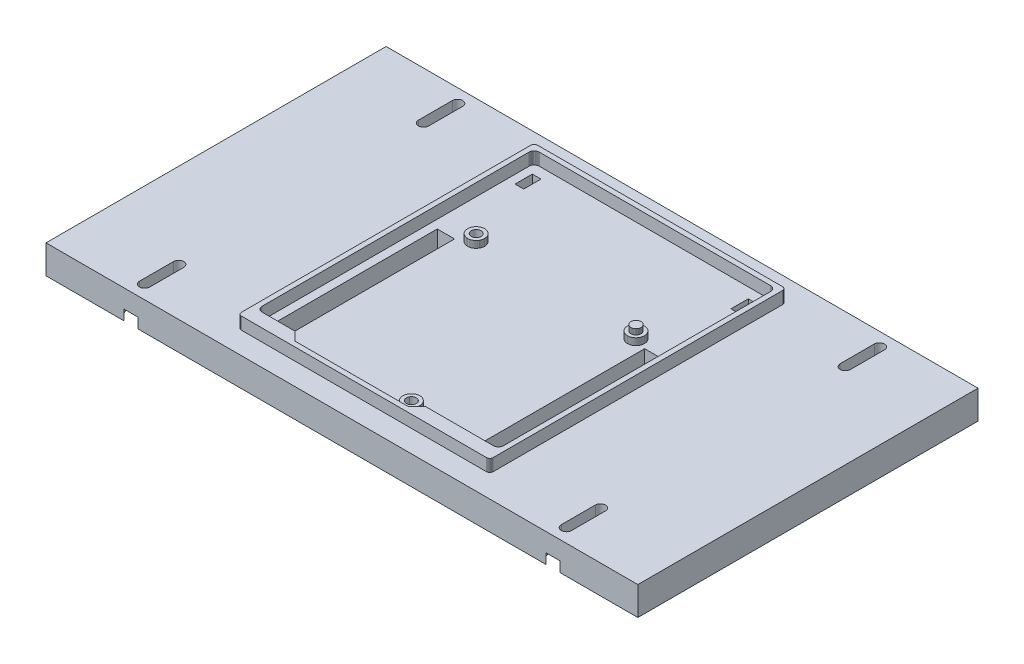
SolidWorks part; units mm, degrees
ref_plane "Front Plane" through (0, 0, 0) normal (0, 0, 1) x (1, 0, 0)
ref_plane "Top Plane" through (0, 0, 0) normal (0, 1, 0) x (1, 0, 0)
ref_plane "Right Plane" through (0, 0, 0) normal (1, 0, 0) x (0, 0, -1)
ref_plane "Plane1" through (0, 0, 0) normal (0, -1, 0) x (1, 0, 0)
sketch "Sketch1" plane through (0, 0, 0) normal (0, -1, 0) x (1, 0, 0)
  line L0 (73, 87.04) -> (1, 87.04)
  line L1 (1, 87.04) -> (0.8264, 87.0248)
  line L2 (0.8264, 87.0248) -> (0.658, 86.9797)
  line L3 (0.658, 86.9797) -> (0.5, 86.906)
  line L4 (0.5, 86.906) -> (0.3572, 86.806)
  line L5 (0.3572, 86.806) -> (0.234, 86.6828)
  line L6 (0.234, 86.6828) -> (0.134, 86.54)
  line L7 (0.134, 86.54) -> (0.0603, 86.382)
  line L8 (0.0603, 86.382) -> (0.0152, 86.2136)
  line L9 (0.0152, 86.2136) -> (0, 86.04)
  line L10 (0, 86.04) -> (0, 1)
  line L11 (0, 1) -> (0.0152, 0.8264)
  line L12 (0.0152, 0.8264) -> (0.0603, 0.658)
  line L13 (0.0603, 0.658) -> (0.134, 0.5)
  line L14 (0.134, 0.5) -> (0.234, 0.3572)
  line L15 (0.234, 0.3572) -> (0.3572, 0.234)
  line L16 (0.3572, 0.234) -> (0.5, 0.134)
  line L17 (0.5, 0.134) -> (0.658, 0.0603)
  line L18 (0.658, 0.0603) -> (0.8264, 0.0152)
  line L19 (0.8264, 0.0152) -> (1, 0)
  line L20 (1, 0) -> (73, 0)
  line L21 (73, 0) -> (73.1736, 0.0152)
  line L22 (73.1736, 0.0152) -> (73.342, 0.0603)
  line L23 (73.342, 0.0603) -> (73.5, 0.134)
  line L24 (73.5, 0.134) -> (73.6428, 0.234)
  line L25 (73.6428, 0.234) -> (73.766, 0.3572)
  line L26 (73.766, 0.3572) -> (73.866, 0.5)
  line L27 (73.866, 0.5) -> (73.9397, 0.658)
  line L28 (73.9397, 0.658) -> (73.9848, 0.8264)
  line L29 (73.9848, 0.8264) -> (74, 1)
  line L30 (74, 1) -> (74, 86.04)
  line L31 (74, 86.04) -> (73.9848, 86.2136)
  line L32 (73.9848, 86.2136) -> (73.9397, 86.382)
  line L33 (73.9397, 86.382) -> (73.866, 86.54)
  line L34 (73.866, 86.54) -> (73.766, 86.6828)
  line L35 (73.766, 86.6828) -> (73.6428, 86.806)
  line L36 (73.6428, 86.806) -> (73.5, 86.906)
  line L37 (73.5, 86.906) -> (73.342, 86.9797)
  line L38 (73.342, 86.9797) -> (73.1736, 87.0248)
  line L39 (73.1736, 87.0248) -> (73, 87.04)
extrude "Boss-Extrude1" add sketch "Sketch1" against normal blind 12
sketch "Sketch2" plane through (0, 12, 0) normal (0, 1, 0) x (-1, 0, 0)
  line L0 (-72.4772, 81.7605) -> (-72.5, 81.5)
  line L1 (-72.5, 81.5) -> (-72.5, 3)
  line L2 (-72.5, 3) -> (-72.4815, 2.7653)
  line L3 (-72.4815, 2.7653) -> (-72.4266, 2.5365)
  line L4 (-72.4266, 2.5365) -> (-72.3365, 2.319)
  line L5 (-72.3365, 2.319) -> (-72.2135, 2.1183)
  line L6 (-72.2135, 2.1183) -> (-72.0607, 1.9393)
  line L7 (-72.0607, 1.9393) -> (-71.8817, 1.7865)
  line L8 (-71.8817, 1.7865) -> (-71.681, 1.6635)
  line L9 (-71.681, 1.6635) -> (-71.4635, 1.5734)
  line L10 (-71.4635, 1.5734) -> (-71.2347, 1.5185)
  line L11 (-71.2347, 1.5185) -> (-71, 1.5)
  line L12 (-71, 1.5) -> (-3, 1.5)
  line L13 (-3, 1.5) -> (-2.7654, 1.5185)
  line L14 (-2.7654, 1.5185) -> (-2.5365, 1.5734)
  line L15 (-2.5365, 1.5734) -> (-2.319, 1.6635)
  line L16 (-2.319, 1.6635) -> (-2.1183, 1.7865)
  line L17 (-2.1183, 1.7865) -> (-1.9393, 1.9393)
  line L18 (-1.9393, 1.9393) -> (-1.7865, 2.1183)
  line L19 (-1.7865, 2.1183) -> (-1.6635, 2.319)
  line L20 (-1.6635, 2.319) -> (-1.5734, 2.5365)
  line L21 (-1.5734, 2.5365) -> (-1.5185, 2.7653)
  line L22 (-1.5185, 2.7653) -> (-1.5, 3)
  line L23 (-1.5, 3) -> (-1.5, 81.5)
  line L24 (-1.5, 81.5) -> (-1.5228, 81.7605)
  line L25 (-1.5228, 81.7605) -> (-1.5905, 82.013)
  line L26 (-1.5905, 82.013) -> (-1.701, 82.25)
  line L27 (-1.701, 82.25) -> (-1.8509, 82.4642)
  line L28 (-1.8509, 82.4642) -> (-2.0358, 82.6491)
  line L29 (-2.0358, 82.6491) -> (-2.25, 82.799)
  line L30 (-2.25, 82.799) -> (-2.487, 82.9095)
  line L31 (-2.487, 82.9095) -> (-2.7395, 82.9772)
  line L32 (-2.7395, 82.9772) -> (-3, 83)
  line L33 (-3, 83) -> (-12.6629, 83)
  line L34 (-12.6629, 83) -> (-15.2029, 85.54)
  line L35 (-15.2029, 85.54) -> (-48.6171, 85.54)
  line L36 (-48.6171, 85.54) -> (-51.1571, 83)
  line L37 (-51.1571, 83) -> (-71, 83)
  line L38 (-71, 83) -> (-71.2605, 82.9772)
  line L39 (-71.2605, 82.9772) -> (-71.513, 82.9095)
  line L40 (-71.513, 82.9095) -> (-71.75, 82.799)
  line L41 (-71.75, 82.799) -> (-71.9642, 82.6491)
  line L42 (-71.9642, 82.6491) -> (-72.1491, 82.4642)
  line L43 (-72.1491, 82.4642) -> (-72.299, 82.25)
  line L44 (-72.299, 82.25) -> (-72.4095, 82.013)
  line L45 (-72.4095, 82.013) -> (-72.4772, 81.7605)
extrude "Cut-Extrude1" cut sketch "Sketch2" against normal blind 3.6
sketch "Sketch3" plane through (0, 8.4, 0) normal (0, 1, 0) x (-1, 0, 0)
  line L0 (-60.6959, 33.662) -> (-60.2749, 33.5492)
  line L1 (-60.2749, 33.5492) -> (-59.88, 33.3651)
  line L2 (-59.88, 33.3651) -> (-59.523, 33.1151)
  line L3 (-59.523, 33.1151) -> (-59.2149, 32.807)
  line L4 (-59.2149, 32.807) -> (-58.9649, 32.45)
  line L5 (-58.9649, 32.45) -> (-58.7808, 32.0551)
  line L6 (-58.7808, 32.0551) -> (-58.668, 31.6341)
  line L7 (-58.668, 31.6341) -> (-58.63, 31.2)
  line L8 (-58.63, 31.2) -> (-58.668, 30.7659)
  line L9 (-58.668, 30.7659) -> (-58.7808, 30.345)
  line L10 (-58.7808, 30.345) -> (-58.9649, 29.95)
  line L11 (-58.9649, 29.95) -> (-59.2149, 29.593)
  line L12 (-59.2149, 29.593) -> (-59.523, 29.2849)
  line L13 (-59.523, 29.2849) -> (-59.88, 29.0349)
  line L14 (-59.88, 29.0349) -> (-60.2749, 28.8508)
  line L15 (-60.2749, 28.8508) -> (-60.6959, 28.738)
  line L16 (-60.6959, 28.738) -> (-61.13, 28.7)
  line L17 (-61.13, 28.7) -> (-61.5641, 28.738)
  line L18 (-61.5641, 28.738) -> (-61.985, 28.8508)
  line L19 (-61.985, 28.8508) -> (-62.38, 29.0349)
  line L20 (-62.38, 29.0349) -> (-62.737, 29.2849)
  line L21 (-62.737, 29.2849) -> (-63.0451, 29.593)
  line L22 (-63.0451, 29.593) -> (-63.2951, 29.95)
  line L23 (-63.2951, 29.95) -> (-63.4792, 30.345)
  line L24 (-63.4792, 30.345) -> (-63.592, 30.7659)
  line L25 (-63.592, 30.7659) -> (-63.63, 31.2)
  line L26 (-63.63, 31.2) -> (-63.592, 31.6341)
  line L27 (-63.592, 31.6341) -> (-63.4792, 32.0551)
  line L28 (-63.4792, 32.0551) -> (-63.2951, 32.45)
  line L29 (-63.2951, 32.45) -> (-63.0451, 32.807)
  line L30 (-63.0451, 32.807) -> (-62.737, 33.1151)
  line L31 (-62.737, 33.1151) -> (-62.38, 33.3651)
  line L32 (-62.38, 33.3651) -> (-61.985, 33.5492)
  line L33 (-61.985, 33.5492) -> (-61.5641, 33.662)
  line L34 (-61.5641, 33.662) -> (-61.13, 33.7)
  line L35 (-61.13, 33.7) -> (-60.6959, 33.662)
extrude "Boss-Extrude2" add sketch "Sketch3" along normal blind 2
sketch "Sketch4" plane through (0, 10.4, 0) normal (0, 1, 0) x (-1, 0, 0)
  line L0 (-61.13, 32.7) -> (-60.8695, 32.6772)
  line L1 (-60.8695, 32.6772) -> (-60.617, 32.6095)
  line L2 (-60.617, 32.6095) -> (-60.38, 32.499)
  line L3 (-60.38, 32.499) -> (-60.1658, 32.3491)
  line L4 (-60.1658, 32.3491) -> (-59.9809, 32.1642)
  line L5 (-59.9809, 32.1642) -> (-59.831, 31.95)
  line L6 (-59.831, 31.95) -> (-59.7205, 31.713)
  line L7 (-59.7205, 31.713) -> (-59.6528, 31.4605)
  line L8 (-59.6528, 31.4605) -> (-59.63, 31.2)
  line L9 (-59.63, 31.2) -> (-59.6528, 30.9395)
  line L10 (-59.6528, 30.9395) -> (-59.7205, 30.687)
  line L11 (-59.7205, 30.687) -> (-59.831, 30.45)
  line L12 (-59.831, 30.45) -> (-59.9809, 30.2358)
  line L13 (-59.9809, 30.2358) -> (-60.1658, 30.0509)
  line L14 (-60.1658, 30.0509) -> (-60.38, 29.901)
  line L15 (-60.38, 29.901) -> (-60.617, 29.7905)
  line L16 (-60.617, 29.7905) -> (-60.8695, 29.7228)
  line L17 (-60.8695, 29.7228) -> (-61.13, 29.7)
  line L18 (-61.13, 29.7) -> (-61.3905, 29.7228)
  line L19 (-61.3905, 29.7228) -> (-61.643, 29.7905)
  line L20 (-61.643, 29.7905) -> (-61.88, 29.901)
  line L21 (-61.88, 29.901) -> (-62.0942, 30.0509)
  line L22 (-62.0942, 30.0509) -> (-62.2791, 30.2358)
  line L23 (-62.2791, 30.2358) -> (-62.429, 30.45)
  line L24 (-62.429, 30.45) -> (-62.5395, 30.687)
  line L25 (-62.5395, 30.687) -> (-62.6072, 30.9395)
  line L26 (-62.6072, 30.9395) -> (-62.63, 31.2)
  line L27 (-62.63, 31.2) -> (-62.6072, 31.4605)
  line L28 (-62.6072, 31.4605) -> (-62.5395, 31.713)
  line L29 (-62.5395, 31.713) -> (-62.429, 31.95)
  line L30 (-62.429, 31.95) -> (-62.2791, 32.1642)
  line L31 (-62.2791, 32.1642) -> (-62.0942, 32.3491)
  line L32 (-62.0942, 32.3491) -> (-61.88, 32.499)
  line L33 (-61.88, 32.499) -> (-61.643, 32.6095)
  line L34 (-61.643, 32.6095) -> (-61.3905, 32.6772)
  line L35 (-61.3905, 32.6772) -> (-61.13, 32.7)
extrude "Boss-Extrude3" add sketch "Sketch4" along normal blind 1.6
sketch "Sketch5" plane through (0, 8.4, 0) normal (0, 1, 0) x (-1, 0, 0)
  line L0 (-14.477, 28.0149) -> (-14.7851, 28.323)
  line L1 (-14.7851, 28.323) -> (-15.0351, 28.68)
  line L2 (-15.0351, 28.68) -> (-15.2192, 29.075)
  line L3 (-15.2192, 29.075) -> (-15.332, 29.4959)
  line L4 (-15.332, 29.4959) -> (-15.37, 29.93)
  line L5 (-15.37, 29.93) -> (-15.332, 30.3641)
  line L6 (-15.332, 30.3641) -> (-15.2192, 30.7851)
  line L7 (-15.2192, 30.7851) -> (-15.0351, 31.18)
  line L8 (-15.0351, 31.18) -> (-14.7851, 31.537)
  line L9 (-14.7851, 31.537) -> (-14.477, 31.8451)
  line L10 (-14.477, 31.8451) -> (-14.12, 32.0951)
  line L11 (-14.12, 32.0951) -> (-13.7251, 32.2792)
  line L12 (-13.7251, 32.2792) -> (-13.3041, 32.392)
  line L13 (-13.3041, 32.392) -> (-12.87, 32.43)
  line L14 (-12.87, 32.43) -> (-12.4359, 32.392)
  line L15 (-12.4359, 32.392) -> (-12.0149, 32.2792)
  line L16 (-12.0149, 32.2792) -> (-11.62, 32.0951)
  line L17 (-11.62, 32.0951) -> (-11.263, 31.8451)
  line L18 (-11.263, 31.8451) -> (-10.9549, 31.537)
  line L19 (-10.9549, 31.537) -> (-10.7049, 31.18)
  line L20 (-10.7049, 31.18) -> (-10.5208, 30.7851)
  line L21 (-10.5208, 30.7851) -> (-10.408, 30.3641)
  line L22 (-10.408, 30.3641) -> (-10.37, 29.93)
  line L23 (-10.37, 29.93) -> (-10.408, 29.4959)
  line L24 (-10.408, 29.4959) -> (-10.5208, 29.075)
  line L25 (-10.5208, 29.075) -> (-10.7049, 28.68)
  line L26 (-10.7049, 28.68) -> (-10.9549, 28.323)
  line L27 (-10.9549, 28.323) -> (-11.263, 28.0149)
  line L28 (-11.263, 28.0149) -> (-11.62, 27.7649)
  line L29 (-11.62, 27.7649) -> (-12.0149, 27.5808)
  line L30 (-12.0149, 27.5808) -> (-12.4359, 27.468)
  line L31 (-12.4359, 27.468) -> (-12.87, 27.43)
  line L32 (-12.87, 27.43) -> (-13.3041, 27.468)
  line L33 (-13.3041, 27.468) -> (-13.7251, 27.5808)
  line L34 (-13.7251, 27.5808) -> (-14.12, 27.7649)
  line L35 (-14.12, 27.7649) -> (-14.477, 28.0149)
extrude "Boss-Extrude4" add sketch "Sketch5" along normal blind 2
sketch "Sketch6" plane through (0, 10.4, 0) normal (0, 1, 0) x (-1, 0, 0)
  line L0 (-12.87, 28.48) -> (-12.6182, 28.502)
  line L1 (-12.6182, 28.502) -> (-12.3741, 28.5674)
  line L2 (-12.3741, 28.5674) -> (-12.145, 28.6743)
  line L3 (-12.145, 28.6743) -> (-11.938, 28.8192)
  line L4 (-11.938, 28.8192) -> (-11.7592, 28.998)
  line L5 (-11.7592, 28.998) -> (-11.6143, 29.205)
  line L6 (-11.6143, 29.205) -> (-11.5074, 29.4341)
  line L7 (-11.5074, 29.4341) -> (-11.442, 29.6782)
  line L8 (-11.442, 29.6782) -> (-11.42, 29.93)
  line L9 (-11.42, 29.93) -> (-11.442, 30.1818)
  line L10 (-11.442, 30.1818) -> (-11.5074, 30.4259)
  line L11 (-11.5074, 30.4259) -> (-11.6143, 30.655)
  line L12 (-11.6143, 30.655) -> (-11.7592, 30.862)
  line L13 (-11.7592, 30.862) -> (-11.938, 31.0408)
  line L14 (-11.938, 31.0408) -> (-12.145, 31.1857)
  line L15 (-12.145, 31.1857) -> (-12.3741, 31.2926)
  line L16 (-12.3741, 31.2926) -> (-12.6182, 31.358)
  line L17 (-12.6182, 31.358) -> (-12.87, 31.38)
  line L18 (-12.87, 31.38) -> (-13.1218, 31.358)
  line L19 (-13.1218, 31.358) -> (-13.3659, 31.2926)
  line L20 (-13.3659, 31.2926) -> (-13.595, 31.1857)
  line L21 (-13.595, 31.1857) -> (-13.802, 31.0408)
  line L22 (-13.802, 31.0408) -> (-13.9808, 30.862)
  line L23 (-13.9808, 30.862) -> (-14.1257, 30.655)
  line L24 (-14.1257, 30.655) -> (-14.2326, 30.4259)
  line L25 (-14.2326, 30.4259) -> (-14.298, 30.1818)
  line L26 (-14.298, 30.1818) -> (-14.32, 29.93)
  line L27 (-14.32, 29.93) -> (-14.298, 29.6782)
  line L28 (-14.298, 29.6782) -> (-14.2326, 29.4341)
  line L29 (-14.2326, 29.4341) -> (-14.1257, 29.205)
  line L30 (-14.1257, 29.205) -> (-13.9808, 28.998)
  line L31 (-13.9808, 28.998) -> (-13.802, 28.8192)
  line L32 (-13.802, 28.8192) -> (-13.595, 28.6743)
  line L33 (-13.595, 28.6743) -> (-13.3659, 28.5674)
  line L34 (-13.3659, 28.5674) -> (-13.1218, 28.502)
  line L35 (-13.1218, 28.502) -> (-12.87, 28.48)
extrude "Cut-Extrude2" cut sketch "Sketch6" against normal blind 8.4
sketch "Sketch7" plane through (0, 8.4, 0) normal (0, 1, 0) x (-1, 0, 0)
  line L0 (-46.3241, 79.538) -> (-46.7451, 79.6508)
  line L1 (-46.7451, 79.6508) -> (-47.14, 79.8349)
  line L2 (-47.14, 79.8349) -> (-47.497, 80.0849)
  line L3 (-47.497, 80.0849) -> (-47.8051, 80.393)
  line L4 (-47.8051, 80.393) -> (-48.0551, 80.75)
  line L5 (-48.0551, 80.75) -> (-48.2392, 81.145)
  line L6 (-48.2392, 81.145) -> (-48.352, 81.5659)
  line L7 (-48.352, 81.5659) -> (-48.39, 82)
  line L8 (-48.39, 82) -> (-48.352, 82.4341)
  line L9 (-48.352, 82.4341) -> (-48.2392, 82.855)
  line L10 (-48.2392, 82.855) -> (-48.0551, 83.25)
  line L11 (-48.0551, 83.25) -> (-47.8051, 83.607)
  line L12 (-47.8051, 83.607) -> (-47.497, 83.9151)
  line L13 (-47.497, 83.9151) -> (-47.14, 84.1651)
  line L14 (-47.14, 84.1651) -> (-46.7451, 84.3492)
  line L15 (-46.7451, 84.3492) -> (-46.3241, 84.462)
  line L16 (-46.3241, 84.462) -> (-45.89, 84.5)
  line L17 (-45.89, 84.5) -> (-45.4559, 84.462)
  line L18 (-45.4559, 84.462) -> (-45.0349, 84.3492)
  line L19 (-45.0349, 84.3492) -> (-44.64, 84.1651)
  line L20 (-44.64, 84.1651) -> (-44.283, 83.9151)
  line L21 (-44.283, 83.9151) -> (-43.9749, 83.607)
  line L22 (-43.9749, 83.607) -> (-43.7249, 83.25)
  line L23 (-43.7249, 83.25) -> (-43.5408, 82.855)
  line L24 (-43.5408, 82.855) -> (-43.428, 82.4341)
  line L25 (-43.428, 82.4341) -> (-43.39, 82)
  line L26 (-43.39, 82) -> (-43.428, 81.5659)
  line L27 (-43.428, 81.5659) -> (-43.5408, 81.145)
  line L28 (-43.5408, 81.145) -> (-43.7249, 80.75)
  line L29 (-43.7249, 80.75) -> (-43.9749, 80.393)
  line L30 (-43.9749, 80.393) -> (-44.283, 80.0849)
  line L31 (-44.283, 80.0849) -> (-44.64, 79.8349)
  line L32 (-44.64, 79.8349) -> (-45.0349, 79.6508)
  line L33 (-45.0349, 79.6508) -> (-45.4559, 79.538)
  line L34 (-45.4559, 79.538) -> (-45.89, 79.5)
  line L35 (-45.89, 79.5) -> (-46.3241, 79.538)
extrude "Boss-Extrude5" add sketch "Sketch7" along normal blind 2
sketch "Sketch8" plane through (0, 10.4, 0) normal (0, 1, 0) x (-1, 0, 0)
  line L0 (-44.462, 82.2518) -> (-44.5274, 82.4959)
  line L1 (-44.5274, 82.4959) -> (-44.6343, 82.725)
  line L2 (-44.6343, 82.725) -> (-44.7792, 82.932)
  line L3 (-44.7792, 82.932) -> (-44.958, 83.1108)
  line L4 (-44.958, 83.1108) -> (-45.165, 83.2557)
  line L5 (-45.165, 83.2557) -> (-45.3941, 83.3626)
  line L6 (-45.3941, 83.3626) -> (-45.6382, 83.428)
  line L7 (-45.6382, 83.428) -> (-45.89, 83.45)
  line L8 (-45.89, 83.45) -> (-46.1418, 83.428)
  line L9 (-46.1418, 83.428) -> (-46.3859, 83.3626)
  line L10 (-46.3859, 83.3626) -> (-46.615, 83.2557)
  line L11 (-46.615, 83.2557) -> (-46.822, 83.1108)
  line L12 (-46.822, 83.1108) -> (-47.0008, 82.932)
  line L13 (-47.0008, 82.932) -> (-47.1457, 82.725)
  line L14 (-47.1457, 82.725) -> (-47.2526, 82.4959)
  line L15 (-47.2526, 82.4959) -> (-47.318, 82.2518)
  line L16 (-47.318, 82.2518) -> (-47.34, 82)
  line L17 (-47.34, 82) -> (-47.318, 81.7482)
  line L18 (-47.318, 81.7482) -> (-47.2526, 81.5041)
  line L19 (-47.2526, 81.5041) -> (-47.1457, 81.275)
  line L20 (-47.1457, 81.275) -> (-47.0008, 81.068)
  line L21 (-47.0008, 81.068) -> (-46.822, 80.8892)
  line L22 (-46.822, 80.8892) -> (-46.615, 80.7443)
  line L23 (-46.615, 80.7443) -> (-46.3859, 80.6374)
  line L24 (-46.3859, 80.6374) -> (-46.1418, 80.572)
  line L25 (-46.1418, 80.572) -> (-45.89, 80.55)
  line L26 (-45.89, 80.55) -> (-45.6382, 80.572)
  line L27 (-45.6382, 80.572) -> (-45.3941, 80.6374)
  line L28 (-45.3941, 80.6374) -> (-45.165, 80.7443)
  line L29 (-45.165, 80.7443) -> (-44.958, 80.8892)
  line L30 (-44.958, 80.8892) -> (-44.7792, 81.068)
  line L31 (-44.7792, 81.068) -> (-44.6343, 81.275)
  line L32 (-44.6343, 81.275) -> (-44.5274, 81.5041)
  line L33 (-44.5274, 81.5041) -> (-44.462, 81.7482)
  line L34 (-44.462, 81.7482) -> (-44.44, 82)
  line L35 (-44.44, 82) -> (-44.462, 82.2518)
extrude "Cut-Extrude3" cut sketch "Sketch8" against normal blind 8.4
sketch "Sketch9" plane through (0, 8.4, 0) normal (0, 1, 0) x (-1, 0, 0)
  line L0 (-67.48, 9.61) -> (-70.02, 9.61)
  line L1 (-70.02, 9.61) -> (-70.02, 4.53)
  line L2 (-70.02, 4.53) -> (-67.48, 4.53)
  line L3 (-67.48, 4.53) -> (-67.48, 9.61)
extrude "Cut-Extrude4" cut sketch "Sketch9" against normal blind 6.4
sketch "Sketch10" plane through (0, 8.4, 0) normal (0, 1, 0) x (-1, 0, 0)
  line L0 (-64.94, 32.47) -> (-64.94, 80.73)
  line L1 (-64.94, 80.73) -> (-70.02, 80.73)
  line L2 (-70.02, 80.73) -> (-70.02, 32.47)
  line L3 (-70.02, 32.47) -> (-64.94, 32.47)
extrude "Cut-Extrude5" cut sketch "Sketch10" against normal blind 6.4
sketch "Sketch11" plane through (0, 8.4, 0) normal (0, 1, 0) x (-1, 0, 0)
  line L0 (-6.52, 4.53) -> (-3.98, 4.53)
  line L1 (-3.98, 4.53) -> (-3.98, 9.61)
  line L2 (-3.98, 9.61) -> (-6.52, 9.61)
  line L3 (-6.52, 9.61) -> (-6.52, 4.53)
extrude "Cut-Extrude6" cut sketch "Sketch11" against normal blind 6.4
sketch "Sketch12" plane through (0, 8.4, 0) normal (0, 1, 0) x (-1, 0, 0)
  line L0 (-3.98, 32.47) -> (-3.98, 80.73)
  line L1 (-3.98, 80.73) -> (-9.06, 80.73)
  line L2 (-9.06, 80.73) -> (-9.06, 32.47)
  line L3 (-9.06, 32.47) -> (-3.98, 32.47)
extrude "Cut-Extrude7" cut sketch "Sketch12" against normal blind 6.4
sketch "Sketch13" plane through (0, 8.4, 0) normal (0, 1, 0) x (1, 0, 0)
  line L0 (73.9848, -0.8264) -> (74, -1) construction
  line L1 (74, -1) -> (74, -86.04) construction
  line L2 (74, -86.04) -> (73.9848, -86.2136) construction
  line L3 (73.9848, -86.2136) -> (73.9397, -86.382) construction
  line L4 (73.9397, -86.382) -> (73.866, -86.54) construction
  line L5 (73.866, -86.54) -> (73.766, -86.6828) construction
  line L6 (73.766, -86.6828) -> (73.6428, -86.806) construction
  line L7 (73.6428, -86.806) -> (73.5, -86.906) construction
  line L8 (73.5, -86.906) -> (73.342, -86.9797) construction
  line L9 (73.342, -86.9797) -> (73.1736, -87.0248) construction
  line L10 (73.1736, -87.0248) -> (73, -87.04) construction
  line L11 (73, -87.04) -> (1, -87.04) construction
  line L12 (73, 0) -> (73.1736, -0.0152) construction
  line L13 (0.8264, -0.0152) -> (1, 0) construction
  line L14 (1, 0) -> (73, 0) construction
  line L15 (73.9848, -0.8264) -> (74, -1)
  line L16 (74, -1) -> (74, -86.04)
  line L17 (74, -86.04) -> (73.9848, -86.2136)
  line L18 (73.9848, -86.2136) -> (73.9397, -86.382)
  line L19 (73.9397, -86.382) -> (73.866, -86.54)
  line L20 (73.866, -86.54) -> (73.766, -86.6828)
  line L21 (73.766, -86.6828) -> (73.6428, -86.806)
  line L22 (73.6428, -86.806) -> (73.5, -86.906)
  line L23 (73.5, -86.906) -> (73.342, -86.9797)
  line L24 (73.342, -86.9797) -> (73.1736, -87.0248)
  line L25 (73.1736, -87.0248) -> (73, -87.04)
  line L26 (73, -87.04) -> (1, -87.04)
  line L27 (73, 0) -> (73.1736, -0.0152)
  line L28 (0.8264, -0.0152) -> (1, 0)
  line L29 (1, 0) -> (73, 0)
  line L30 (73.342, -0.0603) -> (73.5, -0.134) construction
  line L31 (73.5, -0.134) -> (73.6428, -0.234) construction
  line L32 (73.6428, -0.234) -> (73.766, -0.3572) construction
  line L33 (73.766, -0.3572) -> (73.866, -0.5) construction
  line L34 (73.866, -0.5) -> (73.9397, -0.658) construction
  line L35 (73.9397, -0.658) -> (73.9848, -0.8264) construction
  line L36 (73.1736, -0.0152) -> (73.342, -0.0603) construction
  line L37 (73.342, -0.0603) -> (73.5, -0.134)
  line L38 (73.5, -0.134) -> (73.6428, -0.234)
  line L39 (73.6428, -0.234) -> (73.766, -0.3572)
  line L40 (73.766, -0.3572) -> (73.866, -0.5)
  line L41 (73.866, -0.5) -> (73.9397, -0.658)
  line L42 (73.9397, -0.658) -> (73.9848, -0.8264)
  line L43 (73.1736, -0.0152) -> (73.342, -0.0603)
  line L44 (0, -86.04) -> (0, -1) construction
  line L45 (0, -1) -> (0.0152, -0.8264) construction
  line L46 (0.0152, -0.8264) -> (0.0603, -0.658) construction
  line L47 (0.0603, -0.658) -> (0.134, -0.5) construction
  line L48 (0.134, -0.5) -> (0.234, -0.3572) construction
  line L49 (0.234, -0.3572) -> (0.3572, -0.234) construction
  line L50 (0.3572, -0.234) -> (0.5, -0.134) construction
  line L51 (0.5, -0.134) -> (0.658, -0.0603) construction
  line L52 (0.658, -0.0603) -> (0.8264, -0.0152) construction
  line L53 (0, -86.04) -> (0, -1)
  line L54 (0, -1) -> (0.0152, -0.8264)
  line L55 (0.0152, -0.8264) -> (0.0603, -0.658)
  line L56 (0.0603, -0.658) -> (0.134, -0.5)
  line L57 (0.134, -0.5) -> (0.234, -0.3572)
  line L58 (0.234, -0.3572) -> (0.3572, -0.234)
  line L59 (0.3572, -0.234) -> (0.5, -0.134)
  line L60 (0.5, -0.134) -> (0.658, -0.0603)
  line L61 (0.658, -0.0603) -> (0.8264, -0.0152)
  line L62 (1, -87.04) -> (0.8264, -87.0248) construction
  line L63 (0.8264, -87.0248) -> (0.658, -86.9797) construction
  line L64 (0.658, -86.9797) -> (0.5, -86.906) construction
  line L65 (0.5, -86.906) -> (0.3572, -86.806) construction
  line L66 (0.3572, -86.806) -> (0.234, -86.6828) construction
  line L67 (0.234, -86.6828) -> (0.134, -86.54) construction
  line L68 (0.134, -86.54) -> (0.0603, -86.382) construction
  line L69 (0.0603, -86.382) -> (0.0152, -86.2136) construction
  line L70 (0.0152, -86.2136) -> (0, -86.04) construction
  line L71 (1, -87.04) -> (0.8264, -87.0248)
  line L72 (0.8264, -87.0248) -> (0.658, -86.9797)
  line L73 (0.658, -86.9797) -> (0.5, -86.906)
  line L74 (0.5, -86.906) -> (0.3572, -86.806)
  line L75 (0.3572, -86.806) -> (0.234, -86.6828)
  line L76 (0.234, -86.6828) -> (0.134, -86.54)
  line L77 (0.134, -86.54) -> (0.0603, -86.382)
  line L78 (0.0603, -86.382) -> (0.0152, -86.2136)
  line L79 (0.0152, -86.2136) -> (0, -86.04)
  line L80 (37, -87.04) -> (37, -93.52) construction
  line L81 (-50, 6.48) -> (124, 6.48)
  line L82 (-50, 6.48) -> (-50, -93.52)
  line L83 (-50, -93.52) -> (124, -93.52)
  line L84 (124, 6.48) -> (124, -93.52)
  line L85 (37, 0) -> (37, 6.48) construction
  dimension "D1" = 100
  dimension "D2" = 50
extrude "Boss-Extrude6" add sketch "Sketch13" against normal up to surface (8.4 mm away) up to face at (37, 0, 43.52)
sketch "Sketch14" plane through (0, 2, 0) normal (0, 1, 0) x (1, 0, 0)
  line L0 (12.87, -32.43) -> (12.87, -27.43) construction
  line L1 (46.822, -80.8892) -> (46.615, -80.7443) construction
  line L2 (46.615, -80.7443) -> (46.3859, -80.6374) construction
  line L3 (46.3859, -80.6374) -> (46.1418, -80.572) construction
  line L4 (46.1418, -80.572) -> (45.89, -80.55) construction
  line L5 (45.89, -80.55) -> (45.6382, -80.572) construction
  line L6 (45.6382, -80.572) -> (45.3941, -80.6374) construction
  line L7 (45.3941, -80.6374) -> (45.165, -80.7443) construction
  line L8 (45.165, -80.7443) -> (44.958, -80.8892) construction
  line L9 (44.958, -80.8892) -> (44.7792, -81.068) construction
  line L10 (44.7792, -81.068) -> (44.6343, -81.275) construction
  line L11 (44.6343, -81.275) -> (44.5274, -81.5041) construction
  line L12 (44.5274, -81.5041) -> (44.462, -81.7482) construction
  line L13 (44.462, -81.7482) -> (44.44, -82) construction
  line L14 (46.822, -80.8892) -> (46.615, -80.7443) construction
  line L15 (46.615, -80.7443) -> (46.3859, -80.6374) construction
  line L16 (46.3859, -80.6374) -> (46.1418, -80.572) construction
  line L17 (46.1418, -80.572) -> (45.89, -80.55) construction
  line L18 (45.89, -80.55) -> (45.6382, -80.572) construction
  line L19 (45.6382, -80.572) -> (45.3941, -80.6374) construction
  line L20 (45.3941, -80.6374) -> (45.165, -80.7443) construction
  line L21 (45.165, -80.7443) -> (44.958, -80.8892) construction
  line L22 (44.958, -80.8892) -> (44.7792, -81.068) construction
  line L23 (44.7792, -81.068) -> (44.6343, -81.275) construction
  line L24 (44.6343, -81.275) -> (44.5274, -81.5041) construction
  line L25 (44.5274, -81.5041) -> (44.462, -81.7482) construction
  line L26 (44.462, -81.7482) -> (44.44, -82) construction
  line L27 (45.165, -83.2557) -> (45.3941, -83.3626) construction
  line L28 (44.958, -83.1108) -> (45.165, -83.2557) construction
  line L29 (47.0008, -81.068) -> (46.822, -80.8892) construction
  line L30 (44.7792, -82.932) -> (44.958, -83.1108) construction
  line L31 (44.6343, -82.725) -> (44.7792, -82.932) construction
  line L32 (44.6343, -82.725) -> (44.7792, -82.932) construction
  line L33 (44.5274, -82.4959) -> (44.6343, -82.725) construction
  line L34 (44.462, -82.2518) -> (44.5274, -82.4959) construction
  line L35 (44.44, -82) -> (44.462, -82.2518) construction
  line L36 (45.165, -83.2557) -> (45.3941, -83.3626) construction
  line L37 (46.3241, -79.538) -> (45.89, -79.5)
  line L38 (45.89, -79.5) -> (45.4559, -79.538)
  line L39 (45.4559, -79.538) -> (45.0349, -79.6508)
  line L40 (45.0349, -79.6508) -> (44.64, -79.8349)
  line L41 (44.64, -79.8349) -> (44.283, -80.0849)
  line L42 (44.283, -80.0849) -> (43.9749, -80.393)
  line L43 (43.9749, -80.393) -> (43.7249, -80.75)
  line L44 (43.7249, -80.75) -> (43.5408, -81.145)
  line L45 (43.5408, -81.145) -> (43.428, -81.5659)
  line L46 (43.428, -81.5659) -> (43.39, -82)
  line L47 (43.39, -82) -> (43.428, -82.4341)
  line L48 (43.428, -82.4341) -> (43.5408, -82.855)
  line L49 (43.5408, -82.855) -> (43.7249, -83.25)
  line L50 (43.7249, -83.25) -> (43.9749, -83.607)
  line L51 (43.9749, -83.607) -> (44.283, -83.9151)
  line L52 (44.283, -83.9151) -> (44.64, -84.1651)
  line L53 (44.64, -84.1651) -> (45.0349, -84.3492)
  line L54 (45.0349, -84.3492) -> (45.4559, -84.462)
  line L55 (45.4559, -84.462) -> (45.89, -84.5)
  line L56 (45.89, -84.5) -> (46.3241, -84.462)
  line L57 (46.3241, -84.462) -> (46.7451, -84.3492)
  line L58 (46.7451, -84.3492) -> (47.14, -84.1651)
  line L59 (47.14, -84.1651) -> (47.497, -83.9151)
  line L60 (47.497, -83.9151) -> (47.8051, -83.607)
  line L61 (47.8051, -83.607) -> (48.0551, -83.25)
  line L62 (48.0551, -83.25) -> (48.2392, -82.855)
  line L63 (48.2392, -82.855) -> (48.352, -82.4341)
  line L64 (48.352, -82.4341) -> (48.39, -82)
  line L65 (48.39, -82) -> (48.352, -81.5659)
  line L66 (48.352, -81.5659) -> (48.2392, -81.145)
  line L67 (48.2392, -81.145) -> (48.0551, -80.75)
  line L68 (48.0551, -80.75) -> (47.8051, -80.393)
  line L69 (47.8051, -80.393) -> (47.497, -80.0849)
  line L70 (47.497, -80.0849) -> (47.14, -79.8349)
  line L71 (47.14, -79.8349) -> (46.7451, -79.6508)
  line L72 (46.7451, -79.6508) -> (46.3241, -79.538)
  line L73 (46.3241, -79.538) -> (45.89, -79.5) construction
  line L74 (45.89, -79.5) -> (45.4559, -79.538) construction
  line L75 (45.4559, -79.538) -> (45.0349, -79.6508) construction
  line L76 (45.0349, -79.6508) -> (44.64, -79.8349) construction
  line L77 (44.64, -79.8349) -> (44.283, -80.0849) construction
  line L78 (44.283, -80.0849) -> (43.9749, -80.393) construction
  line L79 (43.9749, -80.393) -> (43.7249, -80.75) construction
  line L80 (43.7249, -80.75) -> (43.5408, -81.145) construction
  line L81 (43.5408, -81.145) -> (43.428, -81.5659) construction
  line L82 (43.428, -81.5659) -> (43.39, -82) construction
  line L83 (43.39, -82) -> (43.428, -82.4341) construction
  line L84 (43.428, -82.4341) -> (43.5408, -82.855) construction
  line L85 (43.5408, -82.855) -> (43.7249, -83.25) construction
  line L86 (43.7249, -83.25) -> (43.9749, -83.607) construction
  line L87 (43.9749, -83.607) -> (44.283, -83.9151) construction
  line L88 (44.283, -83.9151) -> (44.64, -84.1651) construction
  line L89 (44.64, -84.1651) -> (45.0349, -84.3492) construction
  line L90 (45.0349, -84.3492) -> (45.4559, -84.462) construction
  line L91 (45.4559, -84.462) -> (45.89, -84.5) construction
  line L92 (45.89, -84.5) -> (46.3241, -84.462) construction
  line L93 (46.3241, -84.462) -> (46.7451, -84.3492) construction
  line L94 (46.7451, -84.3492) -> (47.14, -84.1651) construction
  line L95 (47.14, -84.1651) -> (47.497, -83.9151) construction
  line L96 (47.497, -83.9151) -> (47.8051, -83.607) construction
  line L97 (47.8051, -83.607) -> (48.0551, -83.25) construction
  line L98 (48.0551, -83.25) -> (48.2392, -82.855) construction
  line L99 (48.2392, -82.855) -> (48.352, -82.4341) construction
  line L100 (48.352, -82.4341) -> (48.39, -82) construction
  line L101 (48.39, -82) -> (48.352, -81.5659) construction
  line L102 (48.352, -81.5659) -> (48.2392, -81.145) construction
  line L103 (48.2392, -81.145) -> (48.0551, -80.75) construction
  line L104 (48.0551, -80.75) -> (47.8051, -80.393) construction
  line L105 (47.8051, -80.393) -> (47.497, -80.0849) construction
  line L106 (47.497, -80.0849) -> (47.14, -79.8349) construction
  line L107 (47.14, -79.8349) -> (46.7451, -79.6508) construction
  line L108 (46.7451, -79.6508) -> (46.3241, -79.538) construction
  line L109 (44.958, -83.1108) -> (45.165, -83.2557) construction
  line L110 (47.0008, -81.068) -> (46.822, -80.8892) construction
  line L111 (44.7792, -82.932) -> (44.958, -83.1108) construction
  line L112 (44.6343, -82.725) -> (44.7792, -82.932) construction
  line L113 (44.6343, -82.725) -> (44.7792, -82.932) construction
  line L114 (44.5274, -82.4959) -> (44.6343, -82.725) construction
  line L115 (44.462, -82.2518) -> (44.5274, -82.4959) construction
  line L116 (44.44, -82) -> (44.462, -82.2518) construction
  line L117 (47.1457, -81.275) -> (47.0008, -81.068) construction
  line L118 (47.2526, -81.5041) -> (47.1457, -81.275) construction
  line L119 (47.318, -81.7482) -> (47.2526, -81.5041) construction
  line L120 (47.34, -82) -> (47.318, -81.7482) construction
  line L121 (47.318, -82.2518) -> (47.34, -82) construction
  line L122 (47.2526, -82.4959) -> (47.318, -82.2518) construction
  line L123 (47.1457, -82.725) -> (47.2526, -82.4959) construction
  line L124 (47.0008, -82.932) -> (47.1457, -82.725) construction
  line L125 (46.822, -83.1108) -> (47.0008, -82.932) construction
  line L126 (46.615, -83.2557) -> (46.822, -83.1108) construction
  line L127 (46.3859, -83.3626) -> (46.615, -83.2557) construction
  line L128 (46.1418, -83.428) -> (46.3859, -83.3626) construction
  line L129 (45.89, -83.45) -> (46.1418, -83.428) construction
  line L130 (45.6382, -83.428) -> (45.89, -83.45) construction
  line L131 (45.3941, -83.3626) -> (45.6382, -83.428) construction
  line L132 (47.1457, -81.275) -> (47.0008, -81.068) construction
  line L133 (47.2526, -81.5041) -> (47.1457, -81.275) construction
  line L134 (47.318, -81.7482) -> (47.2526, -81.5041) construction
  line L135 (47.34, -82) -> (47.318, -81.7482) construction
  line L136 (47.318, -82.2518) -> (47.34, -82) construction
  line L137 (47.2526, -82.4959) -> (47.318, -82.2518) construction
  line L138 (47.1457, -82.725) -> (47.2526, -82.4959) construction
  line L139 (47.0008, -82.932) -> (47.1457, -82.725) construction
  line L140 (46.822, -83.1108) -> (47.0008, -82.932) construction
  line L141 (46.615, -83.2557) -> (46.822, -83.1108) construction
  line L142 (46.3859, -83.3626) -> (46.615, -83.2557) construction
  line L143 (46.1418, -83.428) -> (46.3859, -83.3626) construction
  line L144 (45.89, -83.45) -> (46.1418, -83.428) construction
  line L145 (45.6382, -83.428) -> (45.89, -83.45) construction
  line L146 (45.3941, -83.3626) -> (45.6382, -83.428) construction
  line L147 (47.34, -82) -> (44.44, -82) construction
  line L148 (-25, 2.48) -> (-25, -7.52) construction
  line L149 (-23.5, 2.48) -> (-23.5, -7.52)
  line L150 (-26.5, 2.48) -> (-26.5, -7.52)
  line L151 (-25, -79.52) -> (-25, -89.52) construction
  line L152 (-23.5, -79.52) -> (-23.5, -89.52)
  line L153 (-26.5, -79.52) -> (-26.5, -89.52)
  line L154 (-50, 6.48) -> (-50, -93.52) construction
  line L155 (-50, -93.52) -> (124, -93.52) construction
  line L156 (124, 6.48) -> (-50, 6.48) construction
  line L157 (37, 6.48) -> (37, -93.52) construction
  line L158 (-20.5, 2.48) -> (-20.5, -7.52)
  line L159 (-29.5, 2.48) -> (-29.5, -7.52)
  line L160 (-20.5, -79.52) -> (-20.5, -89.52)
  line L161 (-29.5, -79.52) -> (-29.5, -89.52)
  line L162 (94.5, 2.48) -> (94.5, -7.52)
  line L163 (103.5, 2.48) -> (103.5, -7.52)
  line L164 (99, 2.48) -> (99, -7.52) construction
  line L165 (97.5, 2.48) -> (97.5, -7.52)
  line L166 (100.5, 2.48) -> (100.5, -7.52)
  line L167 (94.5, -79.52) -> (94.5, -89.52)
  line L168 (103.5, -79.52) -> (103.5, -89.52)
  line L169 (99, -79.52) -> (99, -89.52) construction
  line L170 (97.5, -79.52) -> (97.5, -89.52)
  line L171 (100.5, -79.52) -> (100.5, -89.52)
  line L183 (14.477, -28.0149) -> (14.12, -27.7649)
  line L184 (14.12, -27.7649) -> (13.7251, -27.5808)
  line L185 (13.7251, -27.5808) -> (13.3041, -27.468)
  line L186 (13.3041, -27.468) -> (12.87, -27.43)
  line L187 (12.87, -27.43) -> (12.4359, -27.468)
  line L188 (12.4359, -27.468) -> (12.0149, -27.5808)
  line L189 (12.0149, -27.5808) -> (11.62, -27.7649)
  line L190 (11.62, -27.7649) -> (11.263, -28.0149)
  line L191 (11.263, -28.0149) -> (10.9549, -28.323)
  line L192 (10.9549, -28.323) -> (10.7049, -28.68)
  line L193 (10.7049, -28.68) -> (10.5208, -29.075)
  line L194 (10.5208, -29.075) -> (10.408, -29.4959)
  line L195 (10.408, -29.4959) -> (10.37, -29.93)
  line L196 (10.37, -29.93) -> (10.408, -30.3641)
  line L197 (10.408, -30.3641) -> (10.5208, -30.7851)
  line L198 (10.5208, -30.7851) -> (10.7049, -31.18)
  line L199 (10.7049, -31.18) -> (10.9549, -31.537)
  line L200 (10.9549, -31.537) -> (11.263, -31.8451)
  line L201 (11.263, -31.8451) -> (11.62, -32.0951)
  line L202 (11.62, -32.0951) -> (12.0149, -32.2792)
  line L203 (12.0149, -32.2792) -> (12.4359, -32.392)
  line L204 (12.4359, -32.392) -> (12.87, -32.43)
  line L205 (12.87, -32.43) -> (13.3041, -32.392)
  line L206 (13.3041, -32.392) -> (13.7251, -32.2792)
  line L207 (13.7251, -32.2792) -> (14.12, -32.0951)
  line L208 (14.12, -32.0951) -> (14.477, -31.8451)
  line L209 (14.477, -31.8451) -> (14.7851, -31.537)
  line L210 (14.7851, -31.537) -> (15.0351, -31.18)
  line L211 (15.0351, -31.18) -> (15.2192, -30.7851)
  line L212 (15.2192, -30.7851) -> (15.332, -30.3641)
  line L213 (15.332, -30.3641) -> (15.37, -29.93)
  line L214 (15.37, -29.93) -> (15.332, -29.4959)
  line L215 (15.332, -29.4959) -> (15.2192, -29.075)
  line L216 (15.2192, -29.075) -> (15.0351, -28.68)
  line L217 (15.0351, -28.68) -> (14.7851, -28.323)
  line L218 (14.7851, -28.323) -> (14.477, -28.0149)
  line L219 (14.477, -28.0149) -> (14.12, -27.7649) construction
  line L220 (14.12, -27.7649) -> (13.7251, -27.5808) construction
  line L221 (13.7251, -27.5808) -> (13.3041, -27.468) construction
  line L222 (13.3041, -27.468) -> (12.87, -27.43) construction
  line L223 (12.87, -27.43) -> (12.4359, -27.468) construction
  line L224 (12.4359, -27.468) -> (12.0149, -27.5808) construction
  line L225 (12.0149, -27.5808) -> (11.62, -27.7649) construction
  line L226 (11.62, -27.7649) -> (11.263, -28.0149) construction
  line L227 (11.263, -28.0149) -> (10.9549, -28.323) construction
  line L228 (10.9549, -28.323) -> (10.7049, -28.68) construction
  line L229 (10.7049, -28.68) -> (10.5208, -29.075) construction
  line L230 (10.5208, -29.075) -> (10.408, -29.4959) construction
  line L231 (10.408, -29.4959) -> (10.37, -29.93) construction
  line L232 (10.37, -29.93) -> (10.408, -30.3641) construction
  line L233 (10.408, -30.3641) -> (10.5208, -30.7851) construction
  line L234 (10.5208, -30.7851) -> (10.7049, -31.18) construction
  line L235 (10.7049, -31.18) -> (10.9549, -31.537) construction
  line L236 (10.9549, -31.537) -> (11.263, -31.8451) construction
  line L237 (11.263, -31.8451) -> (11.62, -32.0951) construction
  line L238 (11.62, -32.0951) -> (12.0149, -32.2792) construction
  line L239 (12.0149, -32.2792) -> (12.4359, -32.392) construction
  line L240 (12.4359, -32.392) -> (12.87, -32.43) construction
  line L241 (12.87, -32.43) -> (13.3041, -32.392) construction
  line L242 (13.3041, -32.392) -> (13.7251, -32.2792) construction
  line L243 (13.7251, -32.2792) -> (14.12, -32.0951) construction
  line L244 (14.12, -32.0951) -> (14.477, -31.8451) construction
  line L245 (14.477, -31.8451) -> (14.7851, -31.537) construction
  line L246 (14.7851, -31.537) -> (15.0351, -31.18) construction
  line L247 (15.0351, -31.18) -> (15.2192, -30.7851) construction
  line L248 (15.2192, -30.7851) -> (15.332, -30.3641) construction
  line L249 (15.332, -30.3641) -> (15.37, -29.93) construction
  line L250 (15.37, -29.93) -> (15.332, -29.4959) construction
  line L251 (15.332, -29.4959) -> (15.2192, -29.075) construction
  line L252 (15.2192, -29.075) -> (15.0351, -28.68) construction
  line L253 (15.0351, -28.68) -> (14.7851, -28.323) construction
  line L254 (14.7851, -28.323) -> (14.477, -28.0149) construction
  circle A0 centre (45.89, -82) radius 1.45
  circle A1 centre (45.89, -82) radius 5
  circle A2 centre (12.87, -29.93) radius 1.45
  circle A3 centre (12.87, -29.93) radius 5
  arc A4 (-23.5, 2.48) -> (-26.5, 2.48) centre (-25, 2.48) ccw
  arc A5 (-26.5, -7.52) -> (-23.5, -7.52) centre (-25, -7.52) ccw
  arc A6 (-23.5, -79.52) -> (-26.5, -79.52) centre (-25, -79.52) ccw
  arc A7 (-26.5, -89.52) -> (-23.5, -89.52) centre (-25, -89.52) ccw
  arc A8 (-29.5, -7.52) -> (-20.5, -7.52) centre (-25, -7.52) ccw
  arc A9 (-20.5, 2.48) -> (-29.5, 2.48) centre (-25, 2.48) ccw
  arc A10 (-29.5, -89.52) -> (-20.5, -89.52) centre (-25, -89.52) ccw
  arc A11 (-20.5, -79.52) -> (-29.5, -79.52) centre (-25, -79.52) ccw
  arc A12 (94.5, 2.48) -> (103.5, 2.48) centre (99, 2.48) cw
  arc A13 (103.5, -7.52) -> (94.5, -7.52) centre (99, -7.52) cw
  arc A14 (97.5, 2.48) -> (100.5, 2.48) centre (99, 2.48) cw
  arc A15 (100.5, -7.52) -> (97.5, -7.52) centre (99, -7.52) cw
  arc A16 (94.5, -79.52) -> (103.5, -79.52) centre (99, -79.52) cw
  arc A17 (103.5, -89.52) -> (94.5, -89.52) centre (99, -89.52) cw
  arc A18 (97.5, -79.52) -> (100.5, -79.52) centre (99, -79.52) cw
  arc A19 (100.5, -89.52) -> (97.5, -89.52) centre (99, -89.52) cw
  point P1 (45.89, -82)
  point P88 (-25, -2.52)
  point P98 (-25, -84.52)
  point P151 (99, -2.52)
  point P162 (99, -84.52)
  dimension "D3" = 10
  dimension "D4" = 10
  dimension "D9" = 1.5
  dimension "D5" = 25
  dimension "D6" = 4
  dimension "D7" = 4
  dimension "D8" = 10
  dimension "D1" = 0
  dimension "D2" = 0
  dimension "D10" = 3
extrude "Cut-Extrude8" cut sketch "Sketch14" against normal through all both and the other way through all contours L150 A5 L149 A4 | L153 A7 L152 A6 | A19 L171 A18 L170 | A0 | A2 | L165 A15 L166 A14 region at (-25, 2, 2.52) region at (-25, 2, 84.52) region at (99, 2, 84.52)
extrude "Cut-Extrude9" cut sketch "Sketch14<4>" along normal blind 3 and the other way through all from surface contours A1 | A3 | L161 A10 L160 A11 | A9 L159 A8 L158 | L162 A13 L163 A12 | L167 A17 L168 A16 starting at face at (-25, 0, 84.52)
sketch "Sketch14<4>" plane through (0, 2, 0) normal (0, 1, 0) x (1, 0, 0) same geometry as "Sketch14"
